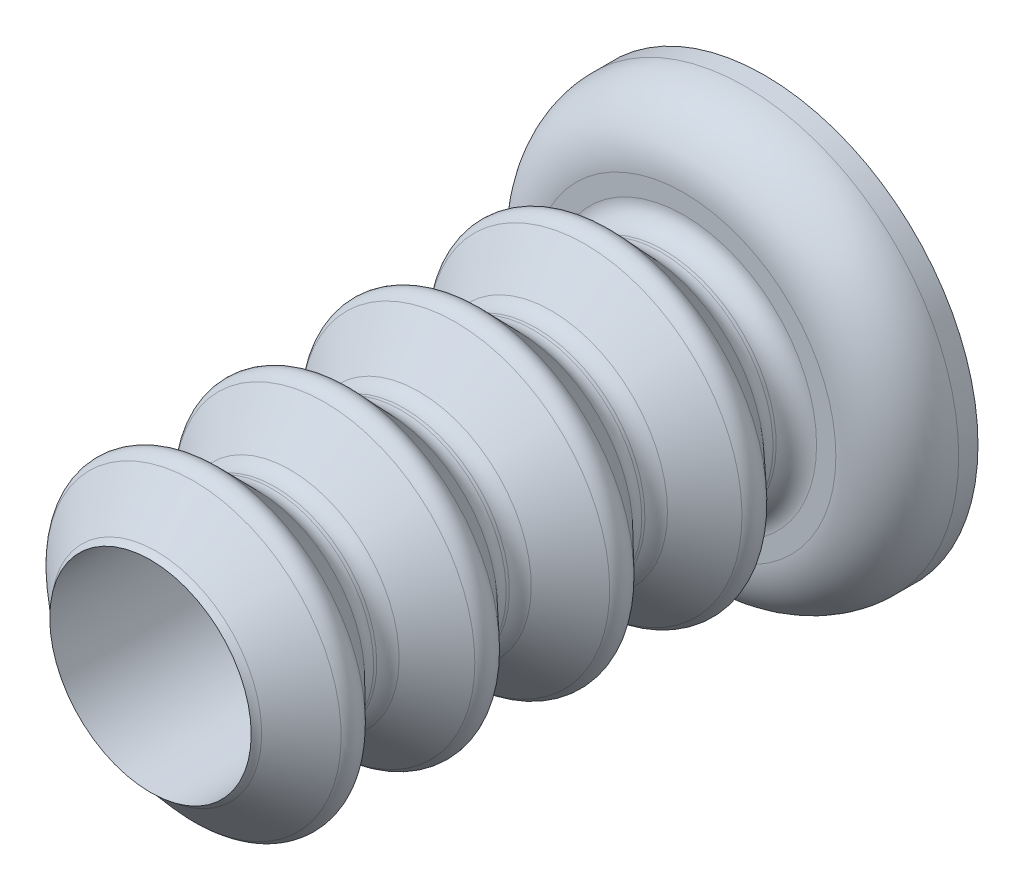
SolidWorks part; units mm, degrees
material "Rubber"
ref_plane "Front Plane" through (0, 0, 0) normal (0, 0, 1) x (1, 0, 0)
ref_plane "Top Plane" through (0, 0, 0) normal (0, 1, 0) x (1, 0, 0)
ref_plane "Right Plane" through (0, 0, 0) normal (1, 0, 0) x (0, 0, -1)
sketch "Sketch20" plane through (0, 0, 0) normal (1, 0, 0) x (0, 0, -1)
  line L0 (-152.3388, 13.9342) -> (-152.7166, 13.9241)
  line L1 (-284.8495, 8.7) -> (-284.8495, 3.2367)
  line L2 (-235.0438, 12.7218) -> (-238.6007, 17.0873)
  line L3 (0, 0) -> (-524.5166, 0) construction
  line L4 (-274.1018, 23.1803) -> (-149.8664, 26.487) construction
  line L5 (-154.6462, 14.7358) -> (-159.1107, 19.5481)
  line L6 (-162.1134, 19.4682) -> (-166.3156, 14.4252)
  line L7 (-170.4685, 14.2732) -> (-175.2673, 19.2237)
  line L8 (-178.2114, 19.1453) -> (-182.74, 13.9466)
  line L9 (-186.8831, 13.8646) -> (-191.4517, 18.7212)
  line L10 (-194.436, 18.6418) -> (-198.7397, 13.549)
  line L11 (-202.8704, 13.3993) -> (-207.7658, 18.3874)
  line L12 (-210.6931, 18.3095) -> (-215.3162, 13.068)
  line L13 (-219.4895, 13.0418) -> (-223.7091, 17.7447)
  line L14 (-226.7553, 17.6636) -> (-230.7187, 12.7429)
  line L16 (-139.8495, 26.487) -> (-139.8495, 0)
  line L17 (-139.8495, 0) -> (-274.8495, 0)
  line L18 (-241.7667, 17.003) -> (-245.0863, 12.4545)
  line L19 (-248.2176, 11.7329) -> (-252.9447, 16.978)
  line L20 (-255.9852, 16.897) -> (-260.4266, 11.4079)
  line L21 (-139.8495, 26.487) -> (-142.2464, 26.487)
  line L22 (-149.8664, 18.867) -> (-149.8664, 16.4733)
  line L23 (-168.1994, 13.512) -> (-168.5772, 13.502)
  line L24 (-184.5877, 13.0758) -> (-184.9654, 13.0658)
  line L25 (-200.6122, 12.6493) -> (-200.99, 12.6393)
  line L26 (-217.1536, 12.209) -> (-217.5313, 12.199)
  line L27 (-232.6293, 11.7971) -> (-233.0071, 11.7871)
  line L28 (-247.0704, 11.4128) -> (-247.4482, 11.4027)
  line L29 (-261.1774, 11.0373) -> (-272.8874, 10.7256)
  line L32 (-278.919, 8.7) -> (-284.8495, 8.7)
  line L33 (-284.8495, 3.2367) -> (-274.8495, 3.2367)
  line L34 (-274.8495, 3.2367) -> (-274.8495, 0)
  line L35 (-139.8495, 26.487) -> (-139.8495, 22.405) construction
  arc A0 (-159.1107, 19.5481) -> (-162.1134, 19.4682) centre (-160.5769, 18.1879) ccw
  arc A1 (-175.2673, 19.2237) -> (-178.2114, 19.1453) centre (-176.7033, 17.8316) ccw
  arc A2 (-191.4517, 18.7212) -> (-194.436, 18.6418) centre (-192.9084, 17.3509) ccw
  arc A3 (-207.7658, 18.3874) -> (-210.6931, 18.3095) centre (-209.1932, 16.9865) ccw
  arc A4 (-223.7091, 17.7447) -> (-226.7553, 17.6636) centre (-225.1977, 16.4091) ccw
  arc A5 (-238.6007, 17.0873) -> (-241.7667, 17.003) centre (-240.1512, 15.824) ccw
  arc A6 (-252.9447, 16.978) -> (-255.9852, 16.897) centre (-254.4304, 15.639) ccw
  arc A7 (-260.4266, 11.4079) -> (-261.1774, 11.0373) centre (-261.204, 12.0369) cw
  arc A8 (-248.2176, 11.7329) -> (-247.4482, 11.4027) centre (-247.4748, 12.4024) ccw
  arc A9 (-274.4406, 10.1422) -> (-278.7909, 8.6968) centre (-278.4721, 15.0065) cw
  arc A10 (-149.8664, 16.4733) -> (-152.3388, 13.9342) centre (-152.4064, 16.4733) cw
  arc A11 (-154.6462, 14.7358) -> (-152.7166, 13.9241) centre (-152.7841, 16.4632) ccw
  arc A12 (-166.3156, 14.4252) -> (-168.1994, 13.512) centre (-168.2669, 16.0511) cw
  arc A13 (-170.4685, 14.2732) -> (-168.5772, 13.502) centre (-168.6447, 16.0411) ccw
  arc A14 (-182.74, 13.9466) -> (-184.5877, 13.0758) centre (-184.6552, 15.6149) cw
  arc A15 (-186.8831, 13.8646) -> (-184.9654, 13.0658) centre (-185.033, 15.6049) ccw
  arc A16 (-198.7397, 13.549) -> (-200.6122, 12.6493) centre (-200.6798, 15.1884) cw
  arc A17 (-202.8704, 13.3993) -> (-200.99, 12.6393) centre (-201.0576, 15.1784) ccw
  arc A18 (-215.3162, 13.068) -> (-217.1536, 12.209) centre (-217.2211, 14.7481) cw
  arc A19 (-219.4895, 13.0418) -> (-217.5313, 12.199) centre (-217.5989, 14.7381) ccw
  arc A20 (-230.7187, 12.7429) -> (-232.6293, 11.7971) centre (-232.6969, 14.3362) cw
  arc A21 (-235.0438, 12.7218) -> (-233.0071, 11.7871) centre (-233.0747, 14.3262) ccw
  arc A22 (-245.0863, 12.4545) -> (-247.0704, 11.4128) centre (-247.138, 13.9519) cw
  arc A23 (-274.4406, 10.1422) -> (-272.8874, 10.7256) centre (-272.8198, 8.1865) cw
  arc A24 (-278.919, 8.7) -> (-278.7909, 8.6968) centre (-278.919, 6.16) cw
  arc A25 (-142.2464, 26.487) -> (-149.8664, 18.867) centre (-142.2464, 18.867) ccw
  arc A26 (-238.6007, 0) -> (-232.6293, 11.7971) centre (-226.4475, 1.2582) cw
  point P27 (-149.8664, 14)
  point P36 (-160.6575, 21.2154)
  point P39 (-176.782, 20.7863)
  point P42 (-192.9884, 20.3549)
  point P45 (-209.2713, 19.9215)
  point P48 (-225.2799, 19.4954)
  point P51 (-240.2383, 19.0973)
  point P54 (-254.5123, 18.7173)
  point P57 (-260.7165, 11.0496)
  point P60 (-247.909, 11.3904)
  point P64 (-153.8649, 13.8936)
  point P73 (-167.051, 13.5426)
  point P76 (-169.6922, 13.4723)
  point P79 (-183.4726, 13.1055)
  point P82 (-186.1033, 13.0355)
  point P85 (-199.4744, 12.6796)
  point P88 (-202.0957, 12.6098)
  point P91 (-216.0479, 12.2385)
  point P94 (-218.7053, 12.1677)
  point P97 (-231.4554, 11.8284)
  point P100 (-234.2552, 11.7539)
  point P103 (-245.8223, 11.446)
  dimension "D4" = 2
  dimension "D5" = 1
  dimension "D2" = 2.54
  dimension "D3" = 7.62
  dimension "D10" = 4
ref_axis "Axis5" through (0, 0, 136.4745) along (0, 0, 1)
revolve "Revolve5" add sketch "Sketch20" angle 360 about L17 region at (0, 8.7235, 184.8275)
sketch "Sketch21" plane through (0, 0, 139.8495) normal (0, 0, -1) x (-1, 0, 0)
  circle A0 centre (0, 0) radius 12.5
  dimension "D1" = 25
extrude "Cut-Extrude1" cut sketch "Sketch21" against normal through all
